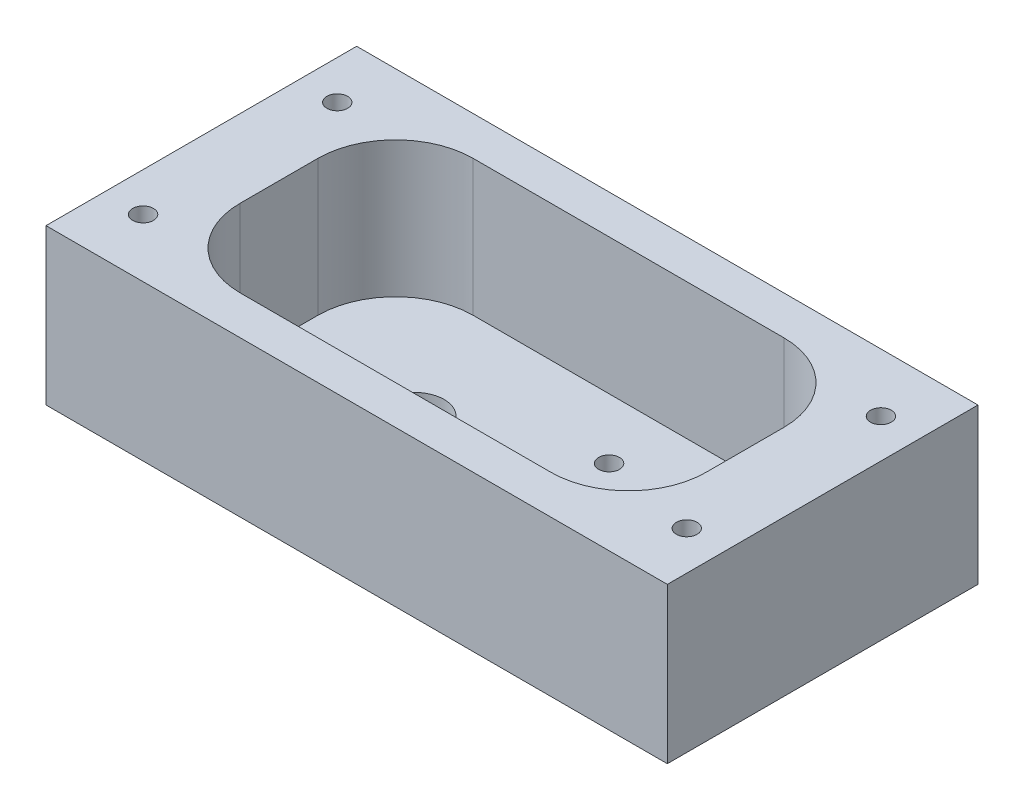
SolidWorks part; units mm, degrees
material "6061 Alloy"
ref_plane "Front Plane" through (0, 0, 0) normal (0, 0, 1) x (1, 0, 0)
ref_plane "Top Plane" through (0, 0, 0) normal (0, 1, 0) x (1, 0, 0)
ref_plane "Right Plane" through (0, 0, 0) normal (1, 0, 0) x (0, 0, -1)
sketch "Sketch1" plane through (0, 0, 0) normal (0, 1, 0) x (1, 0, 0)
  line L1 (-50.8, -25.4) -> (50.8, -25.4)
  line L2 (-50.8, -25.4) -> (-50.8, 25.4)
  line L3 (-50.8, 25.4) -> (50.8, 25.4)
  line L4 (50.8, -25.4) -> (50.8, 25.4)
  line L5 (-50.8, -25.4) -> (50.8, 25.4) construction
  line L6 (-50.8, 25.4) -> (50.8, -25.4) construction
  point P0 (0, 0)
  dimension "D1" = 101.6
  dimension "D2" = 50.8
extrude "Boss-Extrude1" add sketch "Sketch1" along normal blind 25.4
sketch "Sketch2" plane through (0, 0, 0) normal (0, -1, 0) x (1, 0, 0)
  line L0 (-50.8, 0) -> (50.8, 0) construction
  line L1 (-50.8, -25.4) -> (-50.8, 25.4) construction
  line L2 (50.8, 25.4) -> (50.8, -25.4) construction
  line L3 (0, 25.4) -> (0, -25.4) construction
  line L4 (-50.8, 25.4) -> (50.8, 25.4) construction
  line L5 (50.8, -25.4) -> (-50.8, -25.4) construction
  circle A0 centre (-15.875, 0) radius 4.7625
  circle A1 centre (15.875, 0) radius 3
  point P12 (-15.875, 0)
  point P13 (15.875, 0)
  dimension "D3" = 6
  dimension "D4" = 9.525
  dimension "D1" = 31.75
  dimension "D2" = 15.875
extrude "Cut-Extrude1" cut sketch "Sketch2" against normal through all contours A0 | A1
sketch "Sketch3" plane through (0, 25.4, 0) normal (0, 1, 0) x (1, 0, 0)
  line L0 (15.875, 0) -> (-15.875, 0) construction
  line L1 (-25.4, -19.05) -> (25.4, -19.05)
  line L2 (-38.1, -6.35) -> (-38.1, 6.35)
  line L3 (-25.4, 19.05) -> (25.4, 19.05)
  line L4 (38.1, -6.35) -> (38.1, 6.35)
  line L5 (-38.1, -19.05) -> (38.1, 19.05) construction
  line L6 (-38.1, 19.05) -> (38.1, -19.05) construction
  arc A0 (25.4, 19.05) -> (38.1, 6.35) centre (25.4, 6.35) cw
  arc A1 (38.1, -6.35) -> (25.4, -19.05) centre (25.4, -6.35) cw
  arc A2 (-25.4, -19.05) -> (-38.1, -6.35) centre (-25.4, -6.35) cw
  arc A3 (-38.1, 6.35) -> (-25.4, 19.05) centre (-25.4, 6.35) cw
  point P0 (0, 0)
  point P9 (0, 0)
  dimension "D3" = 12.7
  dimension "D1" = 38.1
  dimension "D2" = 76.2
extrude "Cut-Extrude2" cut sketch "Sketch3" against normal blind 22.225
sketch "Sketch4" plane through (0, 0, 0) normal (0, -1, 0) x (1, 0, 0)
  line L0 (-44.45, 25.4) -> (-44.45, -25.4) construction
  line L1 (-50.8, 25.4) -> (50.8, 25.4) construction
  line L2 (50.8, -25.4) -> (-50.8, -25.4) construction
  line L3 (44.45, 25.4) -> (44.45, -25.4) construction
  line L4 (-50.8, -25.4) -> (-50.8, 25.4) construction
  line L5 (50.8, 25.4) -> (50.8, -25.4) construction
  line L6 (-44.45, 0) -> (44.45, 0) construction
  line L7 (6.6826, 9.1924) -> (25.0674, -9.1924) construction
  line L8 (25.0674, 9.1924) -> (6.6826, -9.1924) construction
  circle A1 centre (15.875, 0) radius 3 construction
  point P12 (-44.45, 15.875)
  point P13 (-44.45, -15.875)
  point P14 (44.45, 15.875)
  point P15 (44.45, -15.875)
  point P20 (15.875, 0)
  point P25 (15.875, 0)
  point P27 (6.6826, 9.1924)
  point P28 (25.0674, 9.1924)
  point P29 (25.0674, -9.1924)
  point P30 (6.6826, -9.1924)
  dimension "D1" = 6.35
  dimension "D2" = 6.35
  dimension "D3" = 31.75
  dimension "D4" = 45
  dimension "D5" = 45
  dimension "D6" = 26
hole_wizard "M3 Clearance Hole1" positions "3DSketch1" profile "Sketch5" hole size "M3" standard "ANSI Metric" end condition through all
sketch3d "3DSketch1"
  point P0 (-44.45, 0, 15.875)
  point P3 (-44.45, 0, -15.875)
  point P6 (6.6826, 0, 9.1924)
  point P9 (6.6826, 0, -9.1924)
  point P12 (25.0674, 0, 9.1924)
  point P15 (25.0674, 0, -9.1924)
  point P18 (44.45, 0, 15.875)
  point P21 (44.45, 0, -15.875)
sketch "Sketch5" plane through (-44.45, 0, 15.875) normal (1, 0, 0) x (0, 0, -1)
  line L0 (0, 0) -> (0, 25.4)
  line L1 (0, 25.4) -> (1.7, 25.4)
  line L2 (1.7, 25.4) -> (1.7, 0)
  line L5 (1.7, 0) -> (0, 0)
  line L11 (0, -6.35) -> (0, 107.95) construction
  dimension "Thru Hole Dia." = 3.4
  dimension "Thru Hole Depth" = 25.4
equation "\"D2@Sketch4\"=\"D1@Sketch4\""
